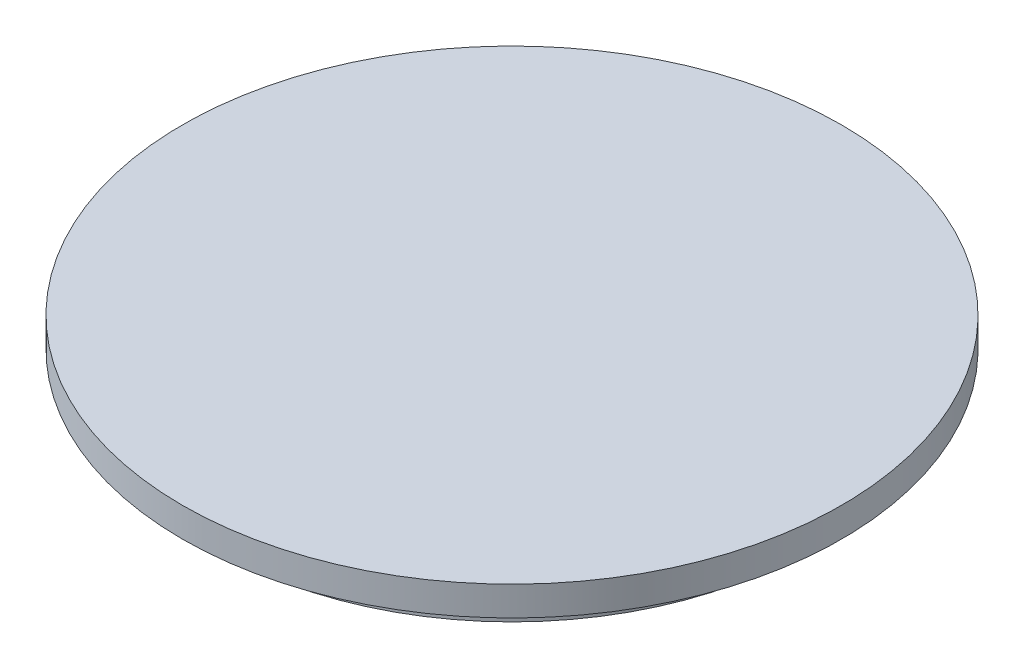
SolidWorks part; units mm, degrees
ref_plane "Ebene vorne" through (0, 0, 0) normal (0, 0, 1) x (1, 0, 0)
ref_plane "Ebene oben" through (0, 0, 0) normal (0, 1, 0) x (1, 0, 0)
ref_plane "Ebene rechts" through (0, 0, 0) normal (1, 0, 0) x (0, 0, -1)
sketch "Skizze1" plane through (0, 0, 0) normal (0, 1, 0) x (1, 0, 0)
  circle A1 centre (0, 0) radius 22.5
extrude "Aufsatz-Linear austragen1" add sketch "Skizze1" along normal blind 2 contours A1
sketch "Skizze2" plane through (0, 0, 0) normal (0, 1, 0) x (1, 0, 0)
  circle A0 centre (0, 0) radius 20
  circle A1 centre (0, 0) radius 18
extrude "Aufsatz-Linear austragen2" add sketch "Skizze2" against normal blind 2
